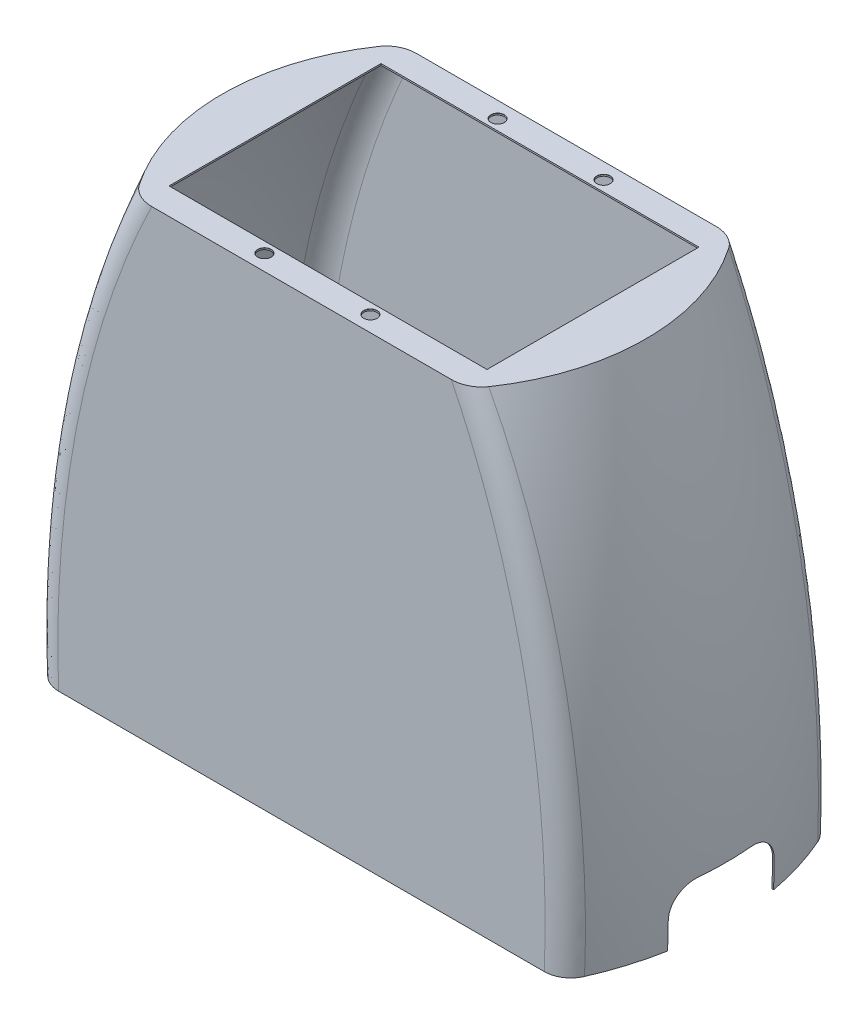
SolidWorks part; units mm, degrees
material "EN AC-46000 (A380)"
ref_plane "Front Plane" through (0, 0, 0) normal (0, 0, 1) x (1, 0, 0)
ref_plane "Top Plane" through (0, 0, 0) normal (0, 1, 0) x (1, 0, 0)
ref_plane "Right Plane" through (0, 0, 0) normal (1, 0, 0) x (0, 0, -1)
sketch "Sketch4" plane through (0, 0, 0) normal (0, 0, 1) x (1, 0, 0)
  line L0 (0, 0) -> (0, 109.0909)
  line L1 (0, 0) -> (0, -72.3906)
  line L2 (0, 0) -> (-129.1246, 0) construction
  line L3 (-129.1246, 0) -> (114.6465, 0) construction
  line L5 (0, 88) -> (-86.3636, 88) construction
  line L6 (0, 100) -> (-76.936, 100) construction
  line L8 (0, 88) -> (54.7138, 88) construction
  line L9 (-40, 88) -> (40, 88)
  line L10 (55, 0) -> (-55, 0)
  arc A1 (-55, 0) -> (-40, 88) centre (164.8616, 7.802) cw
  arc A2 (55, 0) -> (40, 88) centre (-164.8616, 7.802) ccw
  point P0 (0, 0)
  point P4 (-55, 0)
  point P8 (55, 0)
  point P9 (0, 60)
  point P10 (0, 100)
  point P11 (0, 88)
  point P14 (-40, 0)
  point P22 (40, 0)
  dimension "D7" = 40
  dimension "D6" = 40
  dimension "D8" = 220
  dimension "D9" = 40
  dimension "D1" = 55
  dimension "D2" = 55
  dimension "D3" = 60
  dimension "D4" = 100
  dimension "D5" = 88
  dimension "D10" = 40
  dimension "D11" = 88
revolve "Revolve1" add sketch "Sketch4" angle 360 about L0
sketch "Sketch5" plane through (0, 0, 0) normal (0, 1, 0) x (1, 0, 0)
  line L1 (60, 25) -> (-60, 25)
  line L2 (60, 25) -> (60, -25)
  line L3 (60, -25) -> (-60, -25)
  line L4 (-60, 25) -> (-60, -25)
  line L5 (60, 25) -> (-60, -25) construction
  line L6 (60, -25) -> (-60, 25) construction
  line L7 (121.757, 59.1689) -> (-121.757, 59.1689)
  line L8 (121.757, 59.1689) -> (121.757, -59.1689)
  line L9 (121.757, -59.1689) -> (-121.757, -59.1689)
  line L10 (-121.757, 59.1689) -> (-121.757, -59.1689)
  line L11 (121.757, 59.1689) -> (-121.757, -59.1689) construction
  line L12 (121.757, -59.1689) -> (-121.757, 59.1689) construction
  point P0 (0, 0)
  point P6 (0, 0)
  dimension "D1" = 120
  dimension "D2" = 50
extrude "Cut-Extrude1" cut sketch "Sketch5" along normal blind 90 contours L7 L10 L9 L8 L4 L1 L2 L3
fillet "Fillet1" radius 5 4 edges at (39.3081, 68.5515, 25) (39.3081, 68.5515, -25)
shell "Shell1" thickness 0.3
sketch "Sketch7" plane through (0, 0, 0) normal (0, 1, 0) x (1, 0, 0)
  line L0 (25, 20) -> (30, 20)
  line L1 (25, 20) -> (-25, 20)
  line L2 (30, 15) -> (30, -15)
  line L3 (25, -20) -> (-25, -20)
  line L4 (-30, 15) -> (-30, -15)
  line L5 (30, 20) -> (-30, -20) construction
  line L6 (30, -20) -> (-30, 20) construction
  line L7 (30, 20) -> (30, 15)
  line L8 (30, -15) -> (30, -20)
  line L9 (30, -20) -> (25, -20)
  line L10 (-30, -15) -> (-30, -20)
  line L11 (-30, -20) -> (-25, -20)
  line L12 (-30, 15) -> (-30, 20)
  line L13 (-30, 20) -> (-25, 20)
  arc A0 (25, -20) -> (30, -15) centre (25, -15) ccw
  arc A1 (-25, -20) -> (-30, -15) centre (-25, -15) cw
  arc A2 (-25, 20) -> (-30, 15) centre (-25, 15) ccw
  arc A3 (25, 20) -> (30, 15) centre (25, 15) cw
  point P0 (0, 0)
  dimension "D3" = 5
  dimension "D1" = 60
  dimension "D2" = 40
extrude "Cut-Extrude2" cut sketch "Sketch7" along normal blind 90 contours A3 L1 A2 L4 A1 L3 A0 L2 | L0 A3 L7 | A0 L9 L8 | L11 A1 L10 | A2 L13 L12
sketch "Sketch9" plane through (0, 0, 0) normal (1, 0, 0) x (0, 0, -1)
  line L1 (-5, 10) -> (5, 10)
  line L2 (-10, 5) -> (-10, -10)
  line L3 (-10, -10) -> (10, -10)
  line L4 (10, 5) -> (10, -10)
  line L5 (-10, 10) -> (10, -10) construction
  line L6 (-10, -10) -> (10, 10) construction
  arc A0 (-10, 5) -> (-5, 10) centre (-5, 5) cw
  arc A1 (5, 10) -> (10, 5) centre (5, 5) cw
  point P0 (0, 0)
  dimension "D3" = 5
  dimension "D1" = 20
  dimension "D2" = 20
extrude "Cut-Extrude3" cut sketch "Sketch9" against normal blind 76 and the other way blind 76
sketch "Sketch10" plane through (0, 0, 0) normal (1, 0, 0) x (0, 0, -1)
  line L0 (0, 0) -> (0, 97.5254) construction
  line L1 (-29.2533, 31) -> (40.1214, 31) construction
  line L2 (22.6346, 88) -> (-22.6346, 88) construction
  circle A0 centre (-13, 31) radius 6
  circle A1 centre (13, 31) radius 6
  point P3 (0, 31)
  point P6 (-13, 31)
  point P7 (13, 31)
  point P8 (0, 88)
  dimension "D1" = 57
  dimension "D2" = 13
  dimension "D3" = 13
extrude "Cut-Extrude4" cut sketch "Sketch10" against normal blind 70
sketch "Sketch11" plane through (0, 0, 0) normal (0, 1, 0) x (1, 0, 0)
  line L0 (0, 0) -> (0, 39.3017) construction
  line L1 (0, 0) -> (0, -37.2106) construction
  line L2 (-23.1956, 22) -> (25.2704, 22) construction
  line L3 (-22.0886, -22) -> (20.2269, -22) construction
  point P3 (0, 22)
  point P5 (0, -22)
  point P10 (-10, -22)
  point P11 (-10, 22)
  point P12 (10, 22)
  point P13 (10, -22)
  dimension "D1" = 22
  dimension "D2" = 22
  dimension "D3" = 10
  dimension "D4" = 10
  dimension "D5" = 10
  dimension "D6" = 10
hole_wizard "Ø2.5mm Dowel Hole1" positions "Sketch12" profile "Sketch13" hole size "Ø2.5" standard "ISO"
sketch "Sketch12" plane through (0, 88, 0) normal (0, 1, 0) x (1, 0, 0)
  point P0 (-10, 22)
  point P3 (10, 22)
  point P6 (10, -22)
  point P9 (-10, -22)
sketch "Sketch13" plane through (-10, 88, -22) normal (1, 0, 0) x (0, 0, 1)
  line L0 (0, 0) -> (0, 2.7511)
  line L1 (0, 2.7511) -> (1.25, 2)
  line L2 (1.25, 2) -> (1.25, 0.025)
  line L3 (1.25, 0.025) -> (1.275, 0)
  line L5 (1.275, 0) -> (0, 0)
  line L6 (-1.25, 0.025) -> (-1.275, 0) construction
  line L10 (0, 2.7511) -> (-1.25, 2) construction
  line L11 (0, -6.35) -> (0, 107.95) construction
  dimension "Hole Dia." = 2.5
  dimension "Hole Depth" = 2
  dimension "Near C'Sink Dia." = 2.55
  dimension "Near C'Sink Angle" = 90
  dimension "Drill Angle" = 118
